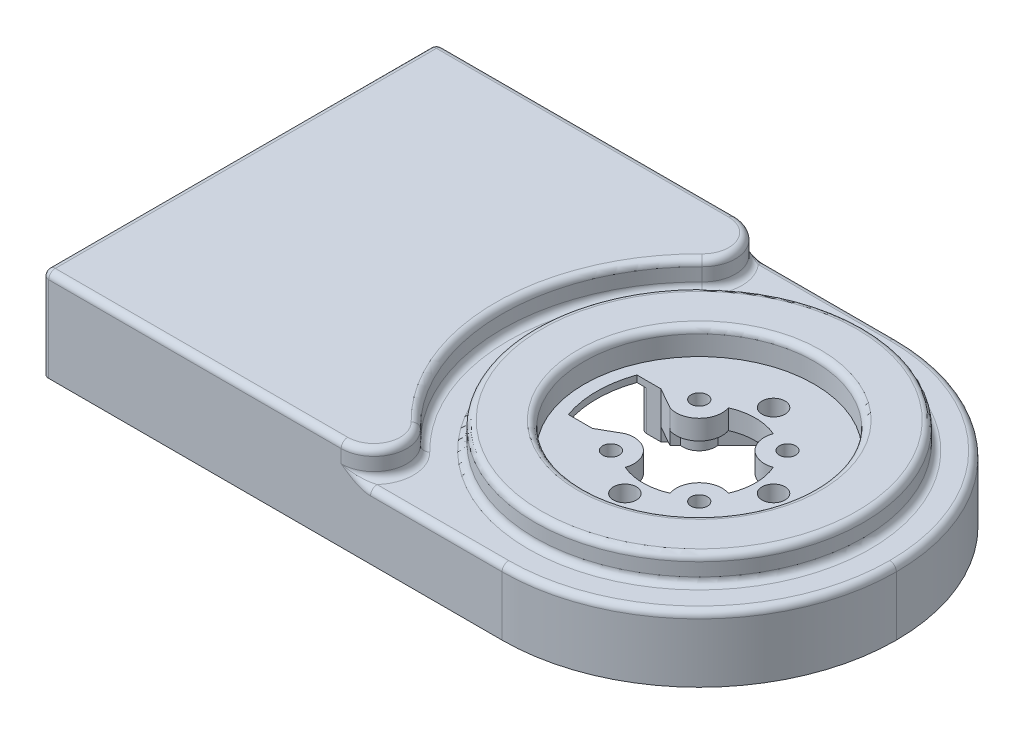
SolidWorks part; units mm, degrees
note: The reader was unsure of these and kept them because the rebuilt part matched: shared geometry of "Sketch1<3>", "Sketch1<4>", "Sketch1<5>", "Sketch1<6>", "Sketch1<8>", "Sketch1<9>", "Sketch28<3>", "Sketch29<3>", "Sketch29<4>".
other "Markup1"
sketch "Sketch33" plane through (30, -5, 30.4442) normal (0.7615, -0.6018, 0.2408) x (0.647, 0.7279, -0.227)
ref_plane "Front Plane" through (0, 0, 0) normal (0, 0, 1) x (1, 0, 0)
ref_plane "Top Plane" through (0, 0, 0) normal (0, 1, 0) x (1, 0, 0)
ref_plane "Right Plane" through (0, 0, 0) normal (1, 0, 0) x (0, 0, -1)
sketch "Sketch1" plane through (0, 0, 0) normal (0, 1, 0) x (1, 0, 0)
  line L5 (30, -30) -> (-30, 30) construction
  line L6 (30, 30) -> (-30, -30) construction
  line L11 (-30, -30) -> (30, -30)
  line L12 (-30, -30) -> (-30, 30)
  line L13 (-30, 30) -> (30, 30)
  line L14 (30, -30) -> (30, 30)
  line L15 (-30, -30) -> (30, 30) construction
  line L16 (-30, 30) -> (30, -30) construction
  line L17 (-30, -30) -> (-70, -30)
  line L18 (-30, -30) -> (-30, 30)
  line L19 (-30, 30) -> (-70, 30)
  line L20 (-70, -30) -> (-70, 30)
  circle A1 centre (0, 0) radius 15.6
  circle A2 centre (0, 0) radius 22.5
  circle A3 centre (0, 0) radius 25.5
  dimension "D1" = 3
  dimension "D6" = 60
  dimension "D7" = 60
  dimension "D8" = 40
extrude "Boss-Extrude1" add sketch "Sketch1" along normal blind 5 contours A1
extrude "Boss-Extrude2" add sketch "Sketch1<3>" along normal blind 5 contours A2 A1
sketch "Sketch1<3>" plane through (0, 0, 0) normal (0, 1, 0) x (1, 0, 0) same geometry as "Sketch1"
extrude "Boss-Extrude3" add sketch "Sketch1<4>" along normal blind 5 contours A3 A2
sketch "Sketch1<4>" plane through (0, 0, 0) normal (0, 1, 0) x (1, 0, 0) same geometry as "Sketch1"
extrude "Boss-Extrude4" add sketch "Sketch1<5>" along normal blind 5 contours L11 L14 L13 L12 A3
sketch "Sketch1<5>" plane through (0, 0, 0) normal (0, 1, 0) x (1, 0, 0) same geometry as "Sketch1"
extrude "Boss-Extrude5" add sketch "Sketch1<6>" along normal blind 5 contours L20 L17 L12 L19
sketch "Sketch1<6>" plane through (0, 0, 0) normal (0, 1, 0) x (1, 0, 0) same geometry as "Sketch1"
sketch "Sketch11" plane through (0, 5, 0) normal (0, 1, 0) x (1, 0, 0)
  circle A1 centre (-6.7175, 6.7175) radius 2.5
  circle A2 centre (-6.7175, -6.7175) radius 2.5
  circle A3 centre (6.7175, 6.7175) radius 2.5
  circle A4 centre (6.7175, -6.7175) radius 2.5
extrude "Cut-Extrude4" cut sketch "Sketch11" against normal blind 6
extrude "Cut-Extrude5" cut sketch "Sketch1<8>" along normal blind 4 contours A2 A1
sketch "Sketch1<8>" plane through (0, 0, 0) normal (0, 1, 0) x (1, 0, 0) same geometry as "Sketch1"
extrude "Boss-Extrude12" add sketch "Sketch1<9>" against normal blind 5 contours L20 L17 L12 L19 | L11 L14 L13 L12 A3
sketch "Sketch1<9>" plane through (0, 0, 0) normal (0, 1, 0) x (1, 0, 0) same geometry as "Sketch1"
sketch "Sketch13" plane through (0, 0, 0) normal (0, -1, 0) x (1, 0, 0)
  line L0 (0, 0) -> (0, 5.75) construction
  line L1 (0, 5.75) -> (0, -5.75) construction
  line L2 (0, 0) -> (5.75, 0) construction
  line L3 (5.75, 0) -> (-5.75, 0) construction
  line L4 (0, 0) -> (6.0104, 6.0104) construction
  line L5 (6.0104, 6.0104) -> (-6.0104, -6.0104) construction
  line L6 (0, 5.75) -> (0, 9.56) construction
  line L7 (0, 9.56) -> (0, -9.56) construction
  line L8 (0, 0) -> (9.56, 0) construction
  line L9 (9.56, 0) -> (-9.56, 0) construction
  circle A6 centre (-6.7175, 6.7175) radius 3.5
  circle A7 centre (6.7175, -6.7175) radius 3.5
  circle A8 centre (6.7175, 6.7175) radius 3.5
  circle A9 centre (-6.7175, -6.7175) radius 3.5
  arc A10 (-1.7448, 11.1746) -> (-11.1746, 1.7448) centre (0, 0) ccw
  circle A12 centre (0, -11.31) radius 1.75
  circle A18 centre (0, 11.31) radius 1.75
  circle A19 centre (-11.31, 0) radius 1.75
  circle A20 centre (11.31, 0) radius 1.75
  circle A21 centre (-11.31, 0) radius 2.75
  circle A22 centre (0, 11.31) radius 2.75
  circle A23 centre (11.31, 0) radius 2.75
  circle A24 centre (0, -11.31) radius 2.75
  circle A25 centre (0, 0) radius 8.56
  arc A26 (11.1746, 1.7448) -> (1.7448, 11.1746) centre (0, 0) ccw
  arc A27 (1.7448, -11.1746) -> (11.1746, -1.7448) centre (0, 0) ccw
  arc A28 (-11.1746, -1.7448) -> (-1.7448, -11.1746) centre (0, 0) ccw
  dimension "D1" = 1
extrude "Cut-Extrude8" cut sketch "Sketch13" against normal blind 10 contours A20 | A18 | A19 | A12 | A7 A25 A8 A6 A9
sketch "Sketch14" plane through (0, 0, 0) normal (0, -1, 0) x (1, 0, 0)
  line L0 (-11.31, 0) -> (0, 11.31)
  line L1 (0, 11.31) -> (11.31, 0)
  line L2 (11.31, 0) -> (0, -11.31)
  line L3 (0, -11.31) -> (-11.31, 0)
extrude "Cut-Extrude9" cut sketch "Sketch14" against normal blind 2
sketch "Sketch17" plane through (0, 0, 0) normal (0, -1, 0) x (1, 0, 0)
  line L0 (0, 0) -> (8.1317, 8.1317)
  line L1 (8.1317, 8.1317) -> (16.2635, 0)
  line L2 (16.2635, 0) -> (0, -16.2635)
  line L3 (0, -16.2635) -> (-16.2635, 0)
  line L4 (-16.2635, 0) -> (0, 16.2635)
  line L5 (0, 16.2635) -> (8.1317, 8.1317)
  circle A0 centre (0, 0) radius 15.6
  arc M9 (-4.2422, -7.0678) -> (-7.0678, -4.2422) centre (-6.7175, -6.7175) cw
  arc M13 (-7.0678, 4.2422) -> (-4.2422, 7.0678) centre (-6.7175, 6.7175) cw
  arc M17 (4.2422, 7.0678) -> (7.0678, 4.2422) centre (6.7175, 6.7175) cw
  arc M21 (7.0678, -4.2422) -> (4.2422, -7.0678) centre (6.7175, -6.7175) cw
  circle M23 centre (0, 0) radius 15.6
extrude "Boss-Extrude13" add sketch "Sketch17" along normal blind 2 contours L4 M23 M13 | L5 L1 M23 M17 | L2 M23 M21 | L3 M23 M9
fillet "Fillet1" radius 30 2 edges at (30, 0, -30) (30, 0, 30)
sketch "Sketch19" plane through (0, 5, 0) normal (0, 1, 0) x (1, 0, 0)
  circle A0 centre (0, 0) radius 17.5
  circle A1 centre (0, 0) radius 25
extrude "Boss-Extrude15" add sketch "Sketch19" along normal blind 4
sketch "Sketch20" plane through (0, -2, 0) normal (0, -1, 0) x (1, 0, 0)
  line L0 (-15.5853, 0.6782) -> (-9.1924, 7.0711) construction
  line L1 (-14.7021, -5.2162) -> (-11.0473, -5.2162)
  line L3 (-14.7021, 5.2162) -> (-11.0473, 5.2162)
  line L5 (-15.6, 0) -> (-11.0473, 5.2162) construction
  line L6 (-15.6, 0) -> (-11.0473, -5.2162) construction
  line L7 (-11.0473, 5.2162) -> (-7.8529, 3.4068)
  line L8 (-7.8529, 3.4068) -> (-7.8529, -3.4068)
  line L9 (-7.8529, -3.4068) -> (-11.0473, -5.2162)
  arc A0 (-15.5853, 0.6782) -> (-15.5853, -0.6782) centre (0, 0) ccw construction
  arc A1 (-14.7021, 5.2162) -> (-14.7021, -5.2162) centre (0, 0) ccw
  point P0 (-15.6, 0)
extrude "Cut-Extrude10" cut sketch "Sketch20" against normal blind 10
sketch "Sketch21" plane through (0, 5, 0) normal (0, 1, 0) x (1, 0, 0)
  line L1 (-70, 30) -> (-24.4949, 30)
  line L2 (-70, 30) -> (-70, -30)
  line L3 (-70, -30) -> (-24.4949, -30)
  arc A0 (-20.9956, 21.4286) -> (-20.9956, -21.4286) centre (0, 0) ccw
  arc A1 (-24.4949, -30) -> (-20.9956, -21.4286) centre (-24.4949, -25) ccw
  arc A2 (-24.4949, 30) -> (-20.9956, 21.4286) centre (-24.4949, 25) cw
  point P11 (0, -30)
  dimension "D1" = 5
extrude "Boss-Extrude16" add sketch "Sketch21" along normal blind 4
sketch "Sketch22" plane through (-70, 0, 0) normal (-1, 0, 0) x (0, 0, 1)
  line L2 (28, 2) -> (28, 6.5)
  line L3 (28, 6.5) -> (17, 6.5)
  line L4 (28, 2) -> (28, -2.5)
  line L6 (28, -2.5) -> (17, -2.5)
  line L9 (28, -2.5) -> (28, 6.5)
  line L11 (28, 6.5) -> (17, 6.5)
  line L14 (17, -2.5) -> (17, 6.5)
sketch "Sketch23" plane through (0, -5, 0) normal (0, -1, 0) x (1, 0, 0)
  line L0 (-70, 28) -> (-70, 17) construction
  line L1 (0, -25.5) -> (-65.5, -25.5)
  line L3 (0, 25.5) -> (-65.5, 25.5)
  line L4 (-70, -25.5) -> (-70, 25.5)
  line L7 (-65.5, 30) -> (-65.5, -30)
  line L8 (-65.5, 25.5) -> (-65.5, -25.5)
  circle A0 centre (0, 0) radius 25.5 construction
  circle A1 centre (0, 0) radius 25.5 construction
  arc A2 (0, 25.5) -> (0, -25.5) centre (0, 0) ccw
  circle M11 centre (0, 0) radius 25.5
  dimension "D1" = 4.5
extrude "Cut-Extrude13" cut sketch "Sketch23" against normal blind 8 contours L3 L8 L1 M11
extrude "Cut-Extrude14" cut sketch "Sketch22" against normal blind 14.2 contours L14 L6 L4 L2 L3
sketch "Sketch24" plane through (0, 3, 0) normal (0, -1, 0) x (1, 0, 0)
  line L0 (-65.5, 25.5) -> (-24.4949, 25.5)
  line L5 (-65.5, 25.5) -> (-65.5, -25.5)
  line L6 (-65.5, -25.5) -> (-24.4949, -25.5)
  arc A3 (-24.145, -24.6429) -> (-24.145, 24.6429) centre (0, 0) cw
  arc A4 (-24.145, 24.6429) -> (-24.4949, 25.5) centre (-24.4949, 25) ccw
  arc A5 (-24.4949, -25.5) -> (-24.145, -24.6429) centre (-24.4949, -25) ccw
extrude "Cut-Extrude16" cut sketch "Sketch24" against normal blind 3
fillet "Fillet8" radius 1 6 edges at (-47.2474, 9, 30) (-70, 9, 0) (-47.2474, 9, -30) (-19.8658, 9, -26.8898) (-30, 9, 0) (-19.8658, 9, 26.8898)
fillet "Fillet9" radius 1 4 edges at (-69.7071, 8.7071, -29.7071) (-69.7071, 8.7071, 29.7071) (-70, 1.5, -30) (-70, 1.5, 30)
fillet "Fillet10" radius 1 10 edges at (0, 9, 17.5) (0, 9, 25) (-19.8658, 5, -26.8898) (-12.2474, 5, -30) (21.2132, 5, -21.2132) (21.2132, 5, 21.2132) (-12.2474, 5, 30) (-19.8658, 5, 26.8898) (-30, 5, 0) (0, 5, 25)
sketch "Sketch27" plane through (0, 6, 0) normal (0, -1, 0) x (1, 0, 0)
  line L0 (-24.4949, 25.5) -> (-55.8, 25.5) construction
  line L1 (-50.0534, 25.5) -> (-32.0534, 25.5)
  line L2 (-50.0534, 25.5) -> (-50.0534, 13.5)
  line L3 (-50.0534, 13.5) -> (-32.0534, 13.5)
  line L4 (-32.0534, 25.5) -> (-32.0534, 13.5)
  line L5 (-52.0534, 27.5) -> (-52.0534, 11.5)
  line L6 (-52.0534, 11.5) -> (-30.0534, 11.5)
  line L7 (-30.0534, 27.5) -> (-30.0534, 11.5)
  line L8 (-52.0534, 27.5) -> (-30.0534, 27.5)
  line M10 (-24.4949, 25.5) -> (-55.8, 25.5)
  dimension "D1" = 12
  dimension "D2" = 18
  dimension "D3" = 2
sketch "Sketch28" plane through (0, 6, 0) normal (0, -1, 0) x (1, 0, 0)
  line L0 (0, -25.5) -> (-65.5, -25.5) construction
  line L2 (-34.6085, -25.5) -> (-34.6085, -6)
  line L4 (-60.6085, -25.5) -> (-60.6085, -6)
  line L9 (-60.6085, -25.5) -> (-60.6085, -27)
  line L10 (-60.6085, -27) -> (-34.6085, -27)
  line L11 (-34.6085, -25.5) -> (-34.6085, -27)
  line L14 (-60.6085, -6) -> (-34.6085, -6)
  line M15 (-65.5, -25.5) -> (-24.4949, -25.5)
  dimension "D3" = 1.5
extrude "Cut-Extrude19" cut sketch "Sketch28" along normal blind 9.5 contours L14 L4 L2 M15 | L11 L9 L10 M15
extrude "Cut-Extrude20" cut sketch "Sketch28<3>" against normal blind 1 contours L14 L4 L2 M15
sketch "Sketch28<3>" plane through (0, 6, 0) normal (0, -1, 0) x (1, 0, 0) same geometry as "Sketch28"
extrude "Cut-Extrude21" cut sketch "Sketch27" against normal blind 1 contours L4 L2 L3 M10
sketch "Sketch29" plane through (-70, 0, 0) normal (-1, 0, 0) x (0, 0, 1)
  line L0 (3.5488, 1.2605) -> (-5.3512, 1.2605)
  line L1 (-0.9512, 4.4605) -> (8.0488, 4.4605)
  line L2 (-0.9512, 4.4605) -> (-0.9512, 1.2605)
  line L3 (-0.9512, 1.2605) -> (8.0488, 1.2605)
  line L4 (8.0488, 4.4605) -> (8.0488, 1.2605)
  line L5 (-5.3512, 1.2605) -> (-5.3512, 6.0605)
  line L6 (-5.3512, 6.0605) -> (12.4488, 6.0605)
  line L7 (12.4488, 6.0605) -> (12.4488, 1.2605)
  line L8 (12.4488, 1.2605) -> (8.0488, 1.2605)
  dimension "D1" = 3.2
  dimension "D2" = 9
sketch "Sketch30" plane through (0, 0, 0) normal (0, -1, 0) x (1, 0, 0)
  line L0 (0, 0) -> (6.7175, -6.7175) construction
  line L1 (0, 0) -> (6.7175, 6.7175) construction
  line L2 (0, 0) -> (9.5, 0) construction
  circle A0 centre (0, 0) radius 9.5
  circle A1 centre (6.7175, 6.7175) radius 1.25
  circle A2 centre (-6.7175, -6.7175) radius 1.25
  circle A3 centre (-6.7175, 6.7175) radius 1.25
  circle A4 centre (6.7175, -6.7175) radius 1.25
  circle A5 centre (-6.7175, 6.7175) radius 2.5
  circle A6 centre (6.7175, -6.7175) radius 2.5
  circle A7 centre (-6.7175, -6.7175) radius 2.5
  circle A8 centre (6.7175, 6.7175) radius 2.5
  arc M14 (-7.0711, 9.1924) -> (-4.2422, 7.0678) centre (-6.7175, 6.7175) cw
  arc M18 (4.2422, 7.0678) -> (7.0711, 9.1924) centre (6.7175, 6.7175) cw
extrude "Boss-Extrude17" add sketch "Sketch30" against normal up to surface (5 mm away) contours A7 A0 A2 | A7 A0 A2 | A5 A0 A3 M14 | A0 A5 A3 M14 | A0 A8 A1 M18 | A8 A0 A1 M18 | A6 A0 A4 | A6 A0 A4
fillet "Fillet11" radius 1 5 edges at (-0.6782, -1, 15.5853) (15.5853, -1, 0.6782) (0.6782, -1, 15.5853) (0.6782, -1, -15.5853) (-0.6782, -1, -15.5853)
fillet "Fillet12" radius 1 2 edges at (-14.7021, 1, -5.2162) (-14.7021, 1, 5.2162)
extrude "Cut-Extrude22" cut sketch "Sketch29" against normal up to surface (4.5 mm away) contours L4 L1 L2 L0 L3 up to face at (-65.5, -0.5, 5.6667)
extrude "Cut-Extrude23" cut sketch "Sketch29<3>" against normal up to surface (4.5 mm away) contours L8 L7 L6 L5 L0 L2 L1 L4 up to face at (-65.5, -0.5, 5.6667)
sketch "Sketch29<3>" plane through (-70, 0, 0) normal (-1, 0, 0) x (0, 0, 1) same geometry as "Sketch29"
extrude "Boss-Extrude18" add sketch "Sketch29<4>" against normal blind 1.5 contours L8 L7 L6 L5 L0 L2 L1 L4
sketch "Sketch29<4>" plane through (-70, 0, 0) normal (-1, 0, 0) x (0, 0, 1) same geometry as "Sketch29"
sketch "Sketch31" plane through (0, 6, 0) normal (0, -1, 0) x (1, 0, 0)
  line L0 (-65.5, -5.3512) -> (-68.5, -5.3512) construction
  line L1 (-68.5, 12.4488) -> (-45.8, 12.4488)
  line L2 (-68.5, 12.4488) -> (-68.5, -5.3512)
  line L3 (-68.5, -5.3512) -> (-45.8, -5.3512)
  line L4 (-45.8, 12.4488) -> (-45.8, -5.3512)
  line L6 (-45.8, 12.4488) -> (-43.8, 12.4488)
  line L7 (-45.8, 12.4488) -> (-45.8, -5.3512)
  line L8 (-45.8, -5.3512) -> (-43.8, -5.3512)
  line L9 (-43.8, 12.4488) -> (-43.8, -5.3512)
  dimension "D1" = 22.7
  dimension "D2" = 2
sketch "Sketch32" plane through (0, 0, 0) normal (0, -1, 0) x (1, 0, 0)
  line L0 (0, 0) -> (0, 9.5) construction
  line L1 (0, 0) -> (6.7175, 6.7175) construction
  circle A0 centre (0, 0) radius 9.5
  circle A1 centre (-6.7175, 6.7175) radius 2.25
  circle A2 centre (6.7175, -6.7175) radius 2.25
  circle A3 centre (-6.7175, -6.7175) radius 2.25
  circle A4 centre (6.7175, 6.7175) radius 2.25
chamfer "Chamfer1" distance 1 angle 45 4 edges at (-6.7175, 0, -7.9675) (6.7175, 0, -7.9675) (6.7175, 0, 5.4675) (-6.7175, 0, 5.4675)
